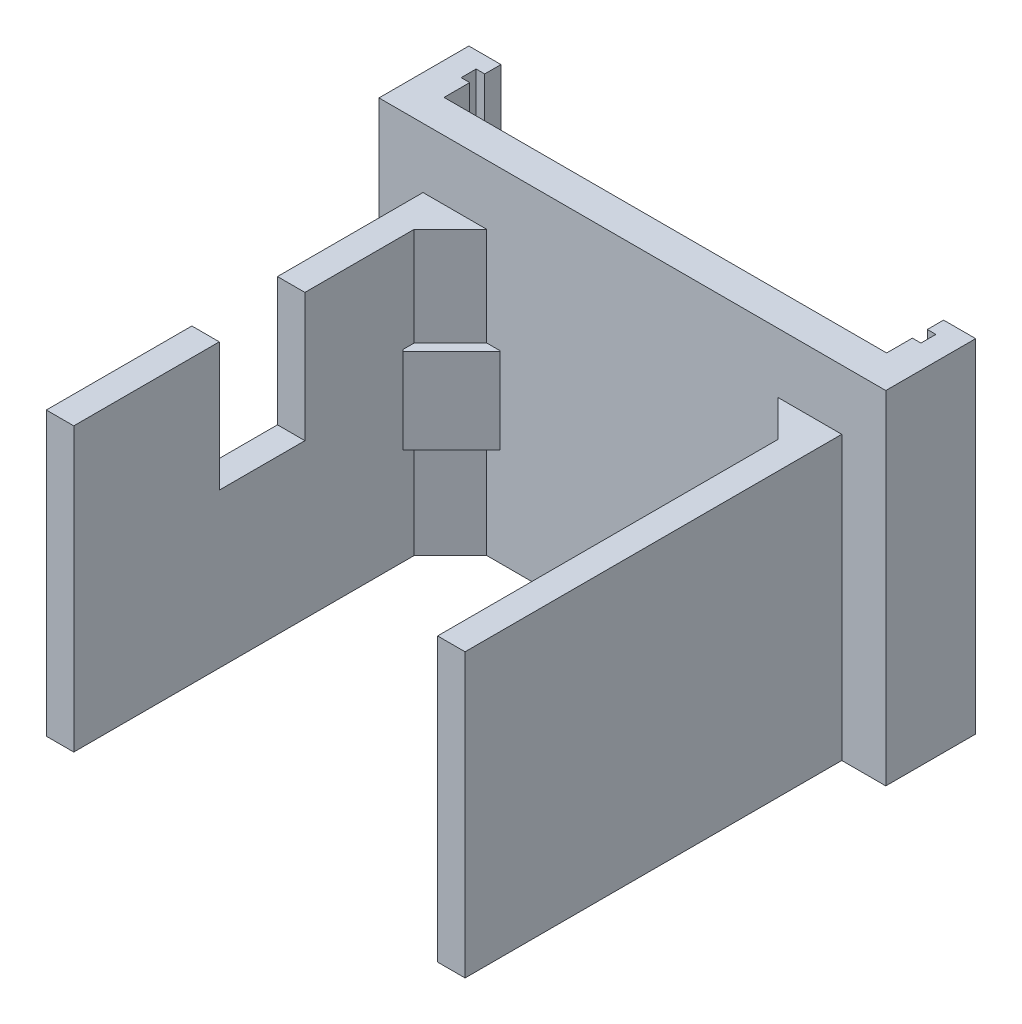
SolidWorks part; units mm, degrees
ref_plane "Front Plane" through (0, 0, 0) normal (0, 0, 1) x (1, 0, 0)
ref_plane "Top Plane" through (0, 0, 0) normal (0, 1, 0) x (1, 0, 0)
ref_plane "Right Plane" through (0, 0, 0) normal (1, 0, 0) x (0, 0, -1)
sketch "Sketch1" plane through (0, 0, 0) normal (0, 1, 0) x (1, 0, 0)
  line L0 (-26.85, 28.85) -> (-25.85, 28.85)
  line L1 (-21.25, -22) -> (21.25, -22)
  line L2 (-21.25, -22) -> (-21.25, 22)
  line L3 (-21.25, 22) -> (21.25, 22)
  line L4 (21.25, -22) -> (21.25, 22)
  line L5 (-21.25, -22) -> (21.25, 22) construction
  line L6 (-21.25, 22) -> (21.25, -22) construction
  line L7 (0, -22) -> (0, 35.4359) construction
  line L8 (-29.6, 22) -> (29.6, 22)
  line L9 (-29.6, 22) -> (-29.6, 32.5)
  line L10 (-29.6, 32.5) -> (-25.85, 32.5)
  line L11 (-25.85, 32.5) -> (-25.85, 30.6)
  line L12 (-25.85, 30.6) -> (-26.85, 30.6)
  line L13 (-26.85, 30.6) -> (-26.85, 28.85)
  line L14 (24.4573, -22) -> (21.25, -22)
  line L15 (21.25, -22) -> (21.25, 22)
  line L16 (24.4573, 22) -> (24.4573, -22)
  line L17 (-24.4573, 22) -> (-24.4573, -22)
  line L18 (-24.4573, -22) -> (-21.25, -22)
  line L19 (23.75, 22) -> (-24.4573, 22)
  line L20 (25.85, 30.6) -> (26.85, 30.6)
  line L21 (25.85, 32.5) -> (25.85, 30.6)
  line L22 (26.85, 30.6) -> (26.85, 28.85)
  line L23 (29.6, 32.5) -> (25.85, 32.5)
  line L24 (29.6, 22) -> (29.6, 32.5)
  line L25 (-25.85, 28.85) -> (-25.85, 25.85)
  line L26 (25.85, 28.85) -> (25.85, 25.85)
  line L27 (26.85, 30.6) -> (26.85, 28.85)
  line L28 (-25.85, 25.85) -> (25.85, 25.85)
  line L29 (26.85, 28.85) -> (25.85, 28.85)
  point P0 (0, 0)
  point P22 (0, 28.4)
  point P30 (0, 25.85)
  dimension "D1" = 44
  dimension "D2" = 59.2
  dimension "D3" = 10.5
  dimension "D4" = 1.9
  dimension "D5" = 3.75
  dimension "D6" = 1.75
  dimension "D7" = 1
  dimension "D8" = 42.5
  dimension "D9" = 3
extrude "Boss-Extrude2" add sketch "Sketch1" along normal blind 33 contours L17 L18 L2 L8 | L16 L8 L4 L14 region at (-22.8536, 0, 0) region at (22.8536, 0, 0)
extrude "Boss-Extrude3" add sketch "Sketch1<6>" along normal blind 40 contours L8 L24 L23 L21 L20 L22 L13 L12 L11 L10 L9 L3 region at (0, 0, -24.8056)
sketch "Sketch1<6>" plane through (0, 0, 0) normal (0, 1, 0) x (1, 0, 0) same geometry as "Sketch1"
chamfer "Chamfer4" distance 4.23 angle 45 2 edges at (21.25, 16.5, -22)
sketch "Sketch2" plane through (-19.51, 0, -19.51) normal (0.7071, 0, 0.7071) x (0.7071, 0, -0.7071)
  line L0 (-2.4607, 16.5) -> (3.5214, 16.5) construction
  line L1 (-2.4607, 0) -> (-2.4607, 33) construction
  line L2 (3.5214, 33) -> (3.5214, 0) construction
  line L3 (0.6036, 0) -> (0.6036, 33) construction
  line L4 (1.7375, 0) -> (-0.5303, 0) construction
  line L5 (1.7375, 33) -> (-0.5303, 33) construction
  line L7 (-3.3964, 11.5) -> (4.6036, 11.5)
  line L8 (-3.3964, 11.5) -> (-3.3964, 21.5)
  line L9 (-3.3964, 21.5) -> (4.6036, 21.5)
  line L10 (4.6036, 11.5) -> (4.6036, 21.5)
  line L11 (-3.3964, 11.5) -> (4.6036, 21.5) construction
  line L12 (-3.3964, 21.5) -> (4.6036, 11.5) construction
  point P12 (0.6036, 16.5)
  dimension "D1" = 10
  dimension "D2" = 8
extrude "Boss-Extrude4" add sketch "Sketch2" along normal blind 1.2
sketch "Sketch3" plane through (19.51, 0, -19.51) normal (-0.7071, 0, 0.7071) x (0.7071, 0, 0.7071)
  line L0 (2.4607, 16.5) -> (-3.5214, 16.5) construction
  line L1 (2.4607, 33) -> (2.4607, 0) construction
  line L2 (-3.5214, 0) -> (-3.5214, 33) construction
  line L3 (-0.6036, 33) -> (-0.6036, 0) construction
  line L4 (-1.7375, 33) -> (0.5303, 33) construction
  line L5 (-1.7375, 0) -> (0.5303, 0) construction
  line L7 (-5.5303, 11.5) -> (4.4697, 11.5)
  line L8 (-5.5303, 11.5) -> (-5.5303, 21.5)
  line L9 (-5.5303, 21.5) -> (4.4697, 21.5)
  line L10 (4.4697, 11.5) -> (4.4697, 21.5)
  line L11 (-5.5303, 11.5) -> (4.4697, 21.5) construction
  line L12 (-5.5303, 21.5) -> (4.4697, 11.5) construction
  point P12 (-0.5303, 16.5)
  dimension "D1" = 10
  dimension "D2" = 10
extrude "Boss-Extrude5" add sketch "Sketch3" along normal blind 1.2
sketch "Sketch4" plane through (0, 33, 0) normal (0, 1, 0) x (1, 0, 0)
  line L0 (-22.8536, -22) -> (-22.8536, 22) construction
  line L1 (-24.4573, -22) -> (-21.25, -22) construction
  line L2 (-24.4573, 22) -> (-17.02, 22) construction
  line L3 (-24.4573, 0) -> (-21.25, 0) construction
  line L4 (-24.4573, 22) -> (-24.4573, -22) construction
  line L5 (-21.25, -22) -> (-21.25, 17.77) construction
  line L7 (-24.4573, -5) -> (-21.25, -5)
  line L8 (-24.4573, -5) -> (-24.4573, 5)
  line L9 (-24.4573, 5) -> (-21.25, 5)
  line L10 (-21.25, -5) -> (-21.25, 5)
  line L11 (-24.4573, -5) -> (-21.25, 5) construction
  line L12 (-24.4573, 5) -> (-21.25, -5) construction
  point P13 (-22.8536, 0)
  dimension "D1" = 10
extrude "Cut-Extrude1" cut sketch "Sketch4" against normal blind 15
